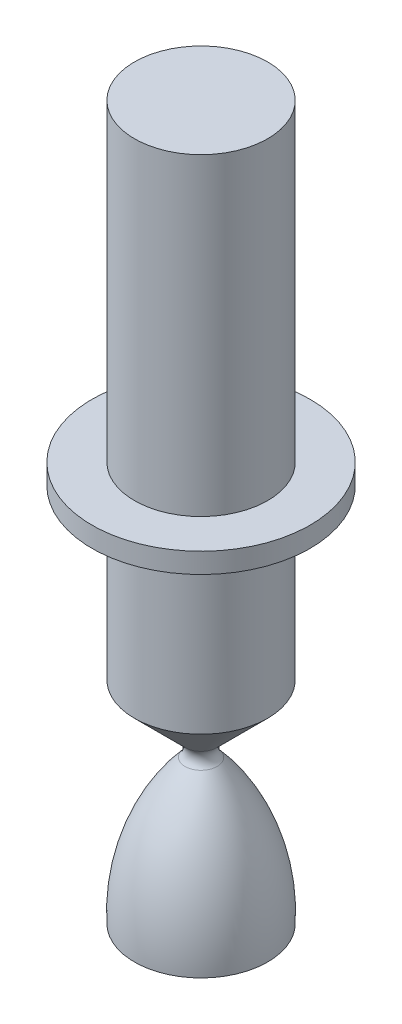
SolidWorks part; units mm, degrees
ref_plane "Front Plane" through (0, 0, 0) normal (0, 0, 1) x (1, 0, 0)
ref_plane "Top Plane" through (0, 0, 0) normal (0, 1, 0) x (1, 0, 0)
ref_plane "Right Plane" through (0, 0, 0) normal (1, 0, 0) x (0, 0, -1)
sketch "Sketch1" plane through (0, 0, 0) normal (0, 0, 1) x (1, 0, 0)
  line L0 (0, 0) -> (17, 0)
  line L1 (0, 0) -> (0, 102)
  line L2 (4.0914, 40.972) -> (17, 53.8805)
  line L3 (17, 53.8805) -> (17, 96.8523)
  line L4 (17, 96.8523) -> (27.8406, 96.8523)
  line L5 (27.8406, 96.8523) -> (27.8406, 102)
  line L6 (27.8406, 102) -> (0, 102)
  line L7 (0, 0) -> (0, 115.2129) construction
  arc A0 (17, 0) -> (4.0914, 36.7809) centre (-34.6191, 2.5396) ccw
  arc A1 (4.0914, 36.7809) -> (4.0914, 40.972) centre (6.187, 38.8765) cw
  dimension "D1" = 17
  dimension "D2" = 102
revolve "Revolve1" add sketch "Sketch1" angle 360 about L7
sketch "Sketch2" plane through (0, 0, 0) normal (0, 0, 1) x (1, 0, 0)
  line L0 (0, 102) -> (0, 182)
  line L1 (27.8406, 102) -> (-27.8406, 102) construction
  line L2 (0, 182) -> (17, 182)
  line L3 (17, 182) -> (17, 102)
  line L4 (17, 102) -> (0, 102)
  line L5 (0, 102) -> (0, 202.5319) construction
  dimension "D1" = 80
  dimension "D2" = 17
revolve "Revolve3" add sketch "Sketch2" angle 360 about L5
